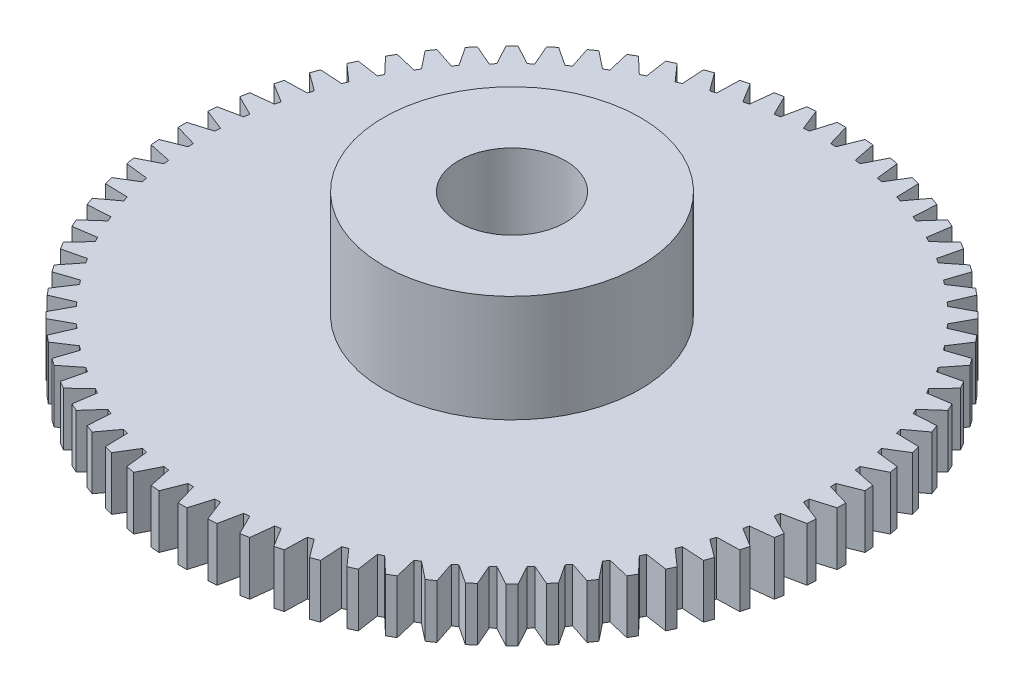
SolidWorks part; units mm, degrees
ref_plane "Front Plane" through (0, 0, 0) normal (0, 0, 1) x (1, 0, 0)
ref_plane "Top Plane" through (0, 0, 0) normal (0, 1, 0) x (1, 0, 0)
ref_plane "Right Plane" through (0, 0, 0) normal (1, 0, 0) x (0, 0, -1)
sketch "Sketch1" plane through (0, 0, 0) normal (0, 1, 0) x (1, 0, 0)
  circle A0 centre (0, 0) radius 3.175
  circle A1 centre (0, 0) radius 7.62
  dimension "D1" = 6.35
  dimension "D2" = 15.24
extrude "Boss-Extrude1" add sketch "Sketch1" along normal blind 9.525 contours A1 A0 region at (-7.4045, 0, 0)
sketch "Sketch2" plane through (0, 0, 0) normal (0, 1, 0) x (1, 0, 0)
  line L0 (0, 0) -> (0, 18.288) construction
  line L1 (-0.635, 18.277) -> (0.635, 18.277)
  line L2 (0, 18.288) -> (0, 19.558) construction
  line L3 (-0.254, 19.558) -> (0.254, 19.558)
  line L4 (-0.254, 19.558) -> (-0.635, 18.277)
  line L5 (0.254, 19.558) -> (0.635, 18.277)
  circle A0 centre (0, 0) radius 18.288
  point P11 (0, 19.558)
  dimension "D1" = 36.576
  dimension "D2" = 1.27
  dimension "D3" = 1.27
  dimension "D4" = 0.508
extrude "Boss-Extrude2" add sketch "Sketch2" along normal blind 3.175 contours L1 A0 region at (0, 0, 0.0002)
extrude "Boss-Extrude3" add sketch "Sketch2<3>" along normal blind 3.175 contours L5 L1 L4 L3
sketch "Sketch2<3>" plane through (0, 0, 0) normal (0, 1, 0) x (1, 0, 0) same geometry as "Sketch2"
pattern_circular "CirPattern1" count 72 over 360 about axis through (0, 9.525, 0) along (0, -1, 0) of "Boss-Extrude3" reverse direction yes
equation "\"Number_Teeth\" = 72"
equation "\"Diametral_Pitch\" = 48"
equation "\"Pitch_Diameter\"= \"Number_Teeth\" * \"1_inch\" / \"Diametral_Pitch\""
equation "\"Tooth_Height\"= .05in"
equation "\"Addendum\"= \"Tooth_Height\" * .4"
equation "\"Dedendum\"= \"Tooth_Height\" * .6"
equation "\"D1@Sketch2\"=\"Pitch_Diameter\"-(2*\"Dedendum\")"
equation "\"D3@Sketch2\"=\"Tooth_Height\""
equation "\"1_inch\"= 1in"
equation "\"D1@CirPattern1\"=\"Number_Teeth\""
